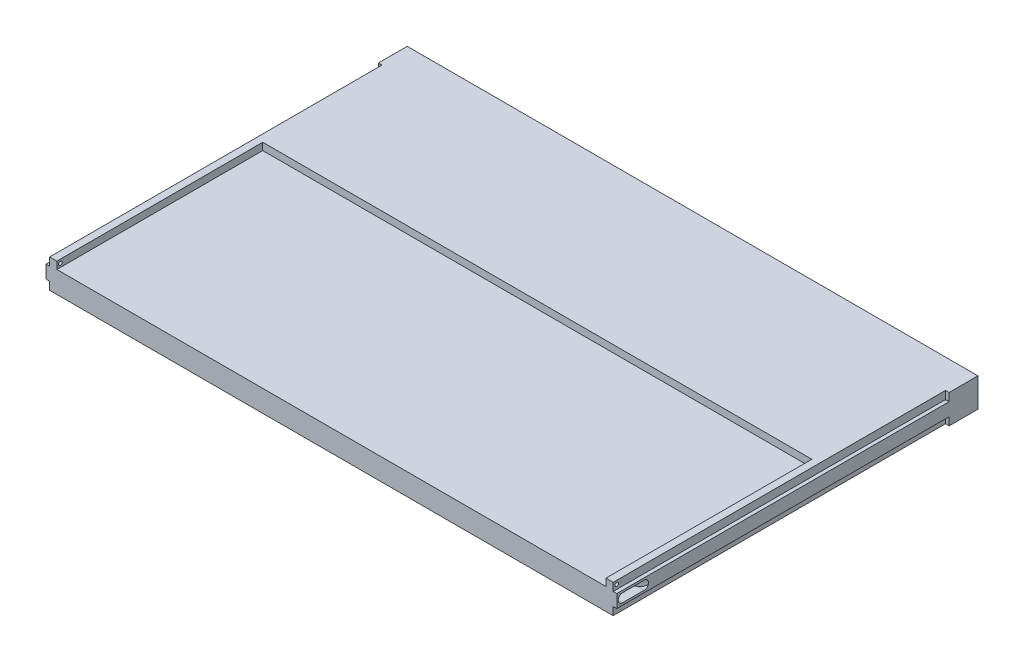
SolidWorks part; units mm, degrees
other "Markup1"
sketch "Sketch12" plane through (250.825, 22.225, 158.75) normal (0.1153, 0.0728, 0.9907) x (0.9687, -0.2289, -0.0959)
material "6061 Alloy"
ref_plane "Front Plane" through (0, 0, 0) normal (0, 0, 1) x (1, 0, 0)
ref_plane "Top Plane" through (0, 0, 0) normal (0, 1, 0) x (1, 0, 0)
ref_plane "Right Plane" through (0, 0, 0) normal (1, 0, 0) x (0, 0, -1)
sketch "Sketch1" plane through (0, 0, 0) normal (0, 1, 0) x (1, 0, 0)
  line L1 (-247.65, 158.75) -> (247.65, 158.75)
  line L2 (-247.65, 158.75) -> (-247.65, -158.75)
  line L3 (-247.65, -158.75) -> (247.65, -158.75)
  line L4 (247.65, 158.75) -> (247.65, -158.75)
  line L5 (-247.65, 158.75) -> (247.65, -158.75) construction
  line L6 (-247.65, -158.75) -> (247.65, 158.75) construction
  point P0 (0, 0)
  dimension "D1" = 495.3
  dimension "D2" = 317.5
extrude "Boss-Extrude1" add sketch "Sketch1" along normal blind 19.05
sketch "Sketch2" plane through (0, 19.05, 0) normal (0, 1, 0) x (1, 0, 0)
  line L0 (-247.65, -158.75) -> (247.65, -158.75) construction
  line L1 (-247.65, 158.75) -> (-241.3, 158.75)
  line L2 (-247.65, 158.75) -> (-247.65, -158.75)
  line L3 (-247.65, -158.75) -> (-241.3, -158.75)
  line L4 (-241.3, 22.225) -> (-241.3, -158.75)
  line L5 (247.65, 158.75) -> (-247.65, 158.75) construction
  line L6 (247.65, 158.75) -> (241.3, 158.75)
  line L7 (247.65, 158.75) -> (247.65, -158.75)
  line L8 (247.65, -158.75) -> (241.3, -158.75)
  line L9 (241.3, 22.225) -> (241.3, -158.75)
  line L10 (-241.3, 158.75) -> (241.3, 158.75)
  line L12 (-241.3, 22.225) -> (241.3, 22.225)
  point P14 (-244.475, -158.75)
  dimension "D1" = 6.35
  dimension "D2" = 180.975
extrude "Boss-Extrude2" add sketch "Sketch2" along normal blind 6.35
sketch "Sketch3" plane through (-247.65, 0, 0) normal (-1, 0, 0) x (0, 0, 1)
  line L0 (158.75, 25.4) -> (158.75, 0) construction
  line L1 (-158.75, 25.4) -> (158.75, 25.4) construction
  circle A0 centre (155.575, 22.225) radius 1.5875
  dimension "D3" = 3.175
  dimension "D1" = 3.175
  dimension "D2" = 3.175
extrude "Cut-Extrude1" cut sketch "Sketch3" against normal through all
sketch "Sketch4" plane through (0, 0, 158.75) normal (0, 0, 1) x (1, 0, 0)
  line L0 (-247.65, 25.4) -> (-247.65, 0) construction
  line L1 (-247.65, 18.415) -> (-250.825, 18.415)
  line L2 (-247.65, 18.415) -> (-247.65, 6.985)
  line L3 (-247.65, 6.985) -> (-250.825, 6.985)
  line L4 (-250.825, 18.415) -> (-250.825, 6.985)
  point P12 (-247.65, 12.7)
  dimension "D1" = 11.43
  dimension "D2" = 3.175
extrude "Boss-Extrude3" add sketch "Sketch4" against normal blind 292.1
sketch "Sketch5" plane through (-247.65, 0, 0) normal (-1, 0, 0) x (0, 0, 1)
  line L0 (-158.75, 0) -> (158.75, 0) construction
  line L1 (-158.75, 25.4) -> (-133.35, 25.4)
  line L2 (-158.75, 25.4) -> (-158.75, 0)
  line L3 (-158.75, 0) -> (-133.35, 0)
  line L4 (-133.35, 25.4) -> (-133.35, 0)
  line L5 (-133.35, 6.985) -> (-133.35, 18.415) construction
extrude "Boss-Extrude4" add sketch "Sketch5" along normal up to surface (3.175 mm away) up to face at (-250.825, 12.7, 12.7)
mirror "Mirror1" about plane through (0, 0, 0) normal (1, 0, 0) of "Boss-Extrude4", "Boss-Extrude3"
sketch "Sketch6" plane through (-247.65, 0, 0) normal (-1, 0, 0) x (0, 0, 1)
  line L0 (153.67, 12.7) -> (134.62, 12.7) construction
  line L1 (153.67, 8.89) -> (134.62, 8.89)
  line L2 (153.67, 16.51) -> (134.62, 16.51)
  line L3 (158.75, 6.985) -> (158.75, 0) construction
  line L5 (158.75, 18.415) -> (158.75, 6.985) construction
  arc A0 (153.67, 8.89) -> (153.67, 16.51) centre (153.67, 12.7) ccw
  arc A1 (134.62, 16.51) -> (134.62, 8.89) centre (134.62, 12.7) ccw
  point P2 (144.145, 12.7)
  point P11 (158.75, 12.7)
  dimension "D1" = 19.05
  dimension "D2" = 5.08
  dimension "D3" = 7.62
extrude "Cut-Extrude2" cut sketch "Sketch6" against normal blind 25.4 from surface starting at face at (-250.825, 12.7, -66.675)
extrude "Cut-Extrude3" cut sketch "Sketch6<2>" along normal blind 25.4 from surface starting at face at (250.825, 12.7, -66.675)
sketch "Sketch6<2>" plane through (-247.65, 0, 0) normal (-1, 0, 0) x (0, 0, 1) same geometry as "Sketch6"
sketch "Sketch11" plane through (0, 0, 0) normal (0, -1, 0) x (1, 0, 0)
  line L0 (-250.825, 130.81) -> (-225.425, 130.81)
  line L1 (-225.425, 130.81) -> (-225.425, 147.32)
  line L2 (-225.425, 147.32) -> (-250.825, 130.81)
  line L3 (-225.425, 134.62) -> (-225.425, 153.67) construction
  dimension "D1" = 10.16
extrude "Boss-Extrude5" add sketch "Sketch11" against normal up to surface (16.51 mm away) from surface up to face at (-238.125, 16.51, 144.145) starting at face at (-238.125, 8.89, 144.145)
mirror "Mirror2" about plane through (0, 0, 0) normal (1, 0, 0) of "Boss-Extrude5"
